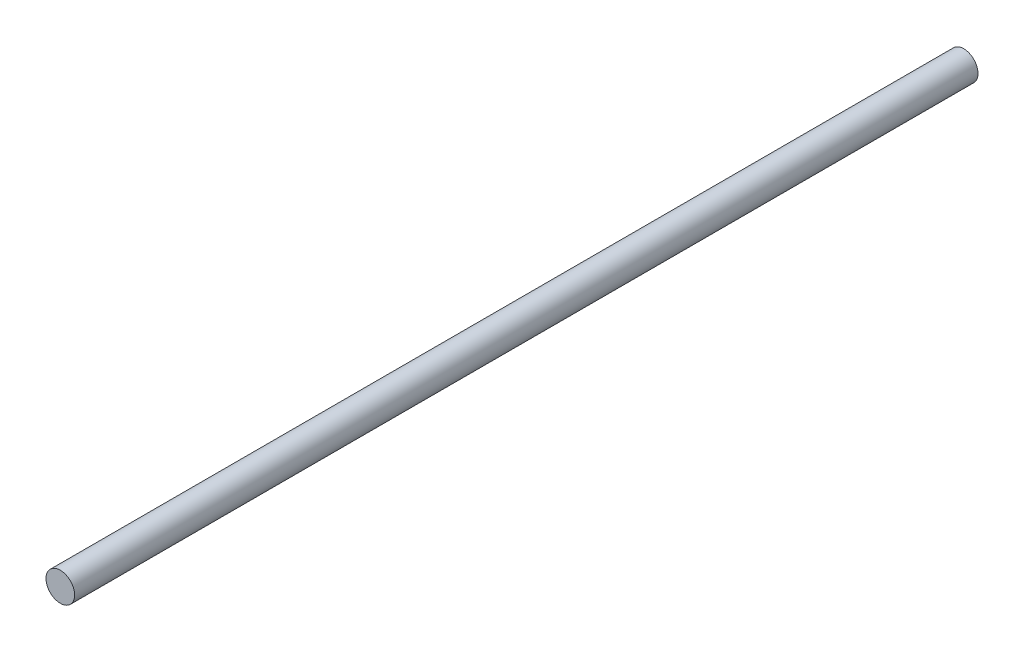
SolidWorks part; units mm, degrees
material "AISI 316 Stainless Steel Sheet (SS)"
ref_plane "Front (1)" through (0, 0, 0) normal (0, 0, 1) x (1, 0, 0)
ref_plane "Top (2)" through (0, 0, 0) normal (0, 1, 0) x (1, 0, 0)
ref_plane "Right (3)" through (0, 0, 0) normal (1, 0, 0) x (0, 0, -1)
ref_axis "X Axis" through (13.5064, 0, 0) along (-1, 0, 0)
ref_axis "Y Axis" through (0, 12.3593, 0) along (0, -1, 0)
ref_axis "Z Axis" through (0, 0, 14.1119) along (0, 0, -1)
sketch "Sketch2" plane through (0, 0, 0) normal (1, 0, 0) x (0, 0, -1)
  line L0 (0, 0) -> (-4, 0) construction
  line L1 (0, 0) -> (252.3477, 0)
  line L2 (0, 0) -> (0, 4)
  line L3 (0, 4) -> (252.3477, 4)
  line L4 (252.3477, 0) -> (252.3477, 4)
  dimension "D1" = 8
  dimension "D2" = 252.3477
revolve "Revolve1" add sketch "Sketch2" angle 360 about L0
cosmetic thread "Cosmetic Thread2"
